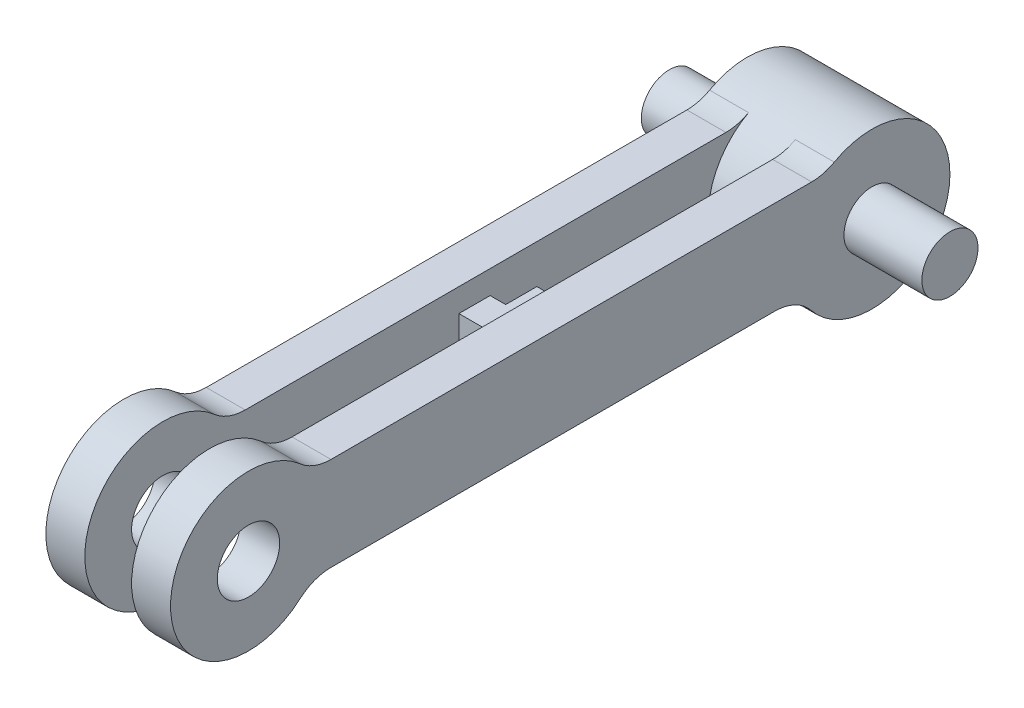
SolidWorks part; units mm, degrees
ref_plane "前视基准面" through (0, 0, 0) normal (0, 0, 1) x (1, 0, 0)
ref_plane "上视基准面" through (0, 0, 0) normal (0, 1, 0) x (1, 0, 0)
ref_plane "右视基准面" through (0, 0, 0) normal (1, 0, 0) x (0, 0, -1)
other "Configuration Table"
sketch "草图1" plane through (0, 0, 0) normal (1, 0, 0) x (0, 0, -1)
  line L1 (0, -3) -> (40, -3)
  line L2 (0, -3) -> (0, 3)
  line L3 (0, 3) -> (40, 3)
  line L4 (40, -3) -> (40, 3)
  circle A0 centre (0, 0) radius 5
  circle A1 centre (40, -1) radius 5
  circle A2 centre (0, 0) radius 2
  circle A3 centre (40, -1) radius 2
  dimension "D1" = 4
  dimension "D4" = 10
  dimension "D5" = 10
  dimension "D2" = 6
  dimension "D3" = 2
  dimension "D6" = 40
extrude "凸台-拉伸1" add sketch "草图1" along normal blind 2.5 contours A0 | L3 L4 L1 L2 | A1
extrude "切除-拉伸2" cut sketch "草图1<3>" against normal through all and the other way through all contours A2 | A3
sketch "草图1<3>" plane through (0, 0, 0) normal (1, 0, 0) x (0, 0, -1) same geometry as "草图1"
fillet "圆角1" radius 3 4 edges at (1.25, -3, -4) (1.25, -3, -35.4174) (1.25, 3, -37) (1.25, 3, -4)
extrude "凸台-拉伸2" add sketch "草图1<4>" against normal blind 1.5 contours A3 L1 A1 L3 L4 | A3 L4 L3 A1 L1 region at (0, 0.0971, -37.2585) region at (0, -3.1385, -37.7087)
sketch "草图1<4>" plane through (0, 0, 0) normal (1, 0, 0) x (0, 0, -1) same geometry as "草图1"
sketch "草图2" plane through (2.5, 0, 0) normal (1, 0, 0) x (0, 0, -1)
  circle A0 centre (40, -1) radius 2
  circle A1 centre (40, -1) radius 1.8
  circle A2 centre (40, -1) radius 2 construction
  dimension "D1" = 3.6
extrude "凸台-拉伸4" add sketch "草图2" along normal blind 5 contours A1 region at (2.5, -1, -40)
extrude "凸台-拉伸5" add sketch "草图1<5>" along normal up to surface and the other way up to surface contours A3 up to face at (2.5, 0, -2) other way up to face at (-1.5, -1, -42)
sketch "草图1<5>" plane through (0, 0, 0) normal (1, 0, 0) x (0, 0, -1) same geometry as "草图1"
sketch "草图3" plane through (0, 0, 0) normal (-1, 0, 0) x (0, 0, 1)
  line L0 (-20, 3) -> (-20, -3) construction
  line L1 (-5.2915, 3) -> (-36.127, 3) construction
  line L2 (-5.2915, -3) -> (-33.755, -3) construction
  line L4 (-21, -1.5) -> (-19, -1.5)
  line L5 (-21, -1.5) -> (-21, 1.5)
  line L6 (-21, 1.5) -> (-19, 1.5)
  line L7 (-19, -1.5) -> (-19, 1.5)
  line L8 (-21, -1.5) -> (-19, 1.5) construction
  line L9 (-21, 1.5) -> (-19, -1.5) construction
  point P0 (-20, 0)
  dimension "D1" = 20
  dimension "D2" = 2
  dimension "D3" = 3
extrude "凸台-拉伸8" add sketch "草图3" along normal blind 1.5
sketch "草图4" plane through (0, 0, -21) normal (0, 0, -1) x (-1, 0, 0)
  line L1 (1.5, 1.5) -> (1, 1.5)
  line L2 (1.5, 1.5) -> (1.5, 0)
  line L3 (1.5, 0) -> (1, 0)
  line L4 (1, 1.5) -> (1, 0)
  dimension "D1" = 1.5
  dimension "D2" = 0.5
extrude "凸台-拉伸9" add sketch "草图4" along normal blind 2
ref_plane "基准面1" through (-1.5, 0, 0) normal (-1, 0, 0) x (0, 0, 1)
mirror "镜向3" about plane through (-1.5, 0, 0) normal (-1, 0, 0) of bodies 118 108
